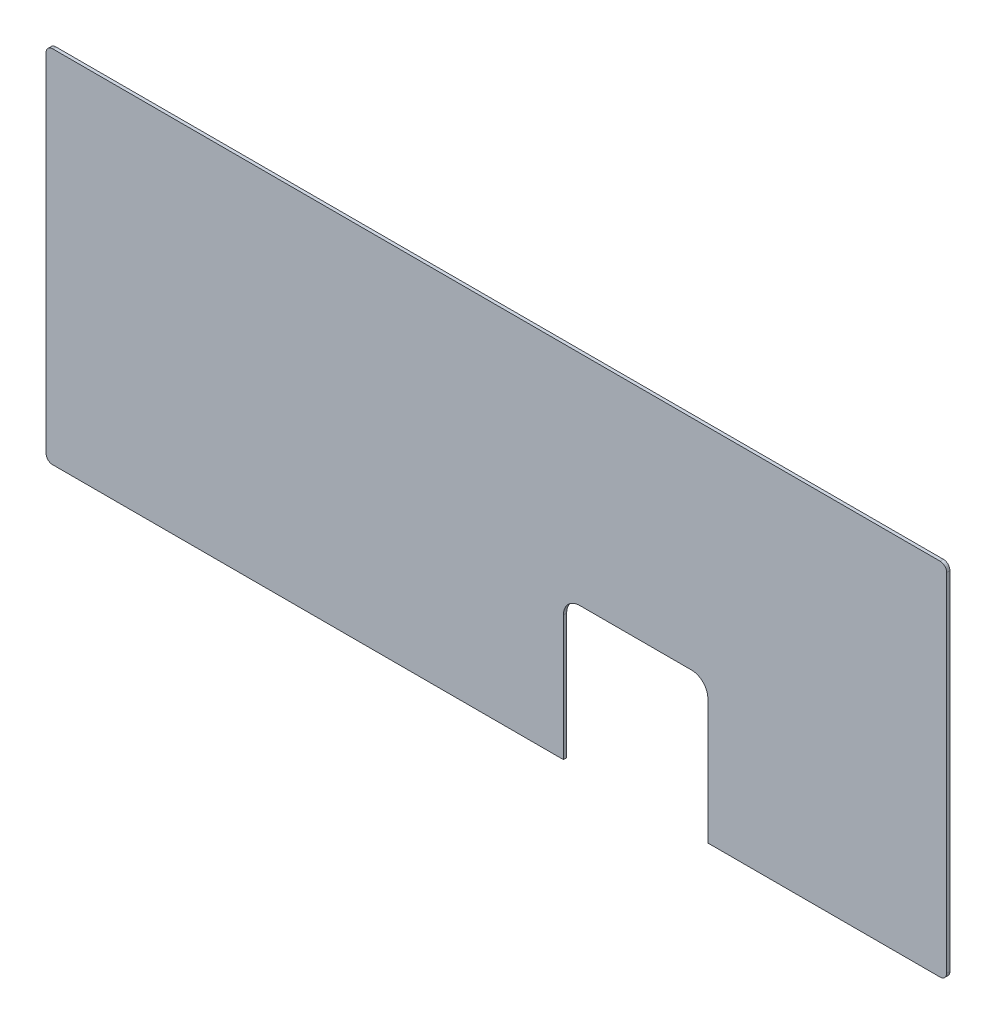
SolidWorks part; units mm, degrees
ref_plane "Спереди" through (0, 0, 0) normal (0, 0, 1) x (1, 0, 0)
ref_plane "Сверху" through (0, 0, 0) normal (0, 1, 0) x (1, 0, 0)
ref_plane "Справа" through (0, 0, 0) normal (1, 0, 0) x (0, 0, -1)
sketch "Эскиз1" plane through (0, 0, 0) normal (0, 0, 1) x (1, 0, 0)
  line L0 (89.221, -66.774) -> (89.221, -28.5207)
  line L1 (-66.75, -66.774) -> (89.221, -66.774)
  line L2 (-68.75, -64.774) -> (-68.75, 41.226)
  line L3 (-66.75, 43.226) -> (204.25, 43.226)
  line L4 (206.25, -64.774) -> (206.25, 41.226)
  line L5 (-68.75, -66.774) -> (206.25, 43.226) construction
  line L6 (-68.75, 43.226) -> (206.25, -66.774) construction
  line L7 (94.221, -23.5207) -> (128.3293, -23.5207)
  line L8 (133.3293, -28.5207) -> (133.3293, -66.774)
  line L9 (133.3293, -66.774) -> (204.25, -66.774)
  arc A0 (-66.75, -66.774) -> (-68.75, -64.774) centre (-66.75, -64.774) cw
  arc A1 (206.25, -64.774) -> (204.25, -66.774) centre (204.25, -64.774) cw
  arc A2 (206.25, 41.226) -> (204.25, 43.226) centre (204.25, 41.226) ccw
  arc A3 (-66.75, 43.226) -> (-68.75, 41.226) centre (-66.75, 41.226) ccw
  arc A4 (133.3293, -28.5207) -> (128.3293, -23.5207) centre (128.3293, -28.5207) ccw
  arc A5 (94.221, -23.5207) -> (89.221, -28.5207) centre (94.221, -28.5207) ccw
  point P0 (0, 0)
  dimension "D3" = 2
  dimension "D4" = 5
  dimension "D1" = 275
  dimension "D2" = 110
base flange "Базовая кромка1" sketch "Эскиз1" thickness 1 reverse thickness direction no parameters "D1"=0.7366
sketch "Сгиб-Линии1" [suppressed]
sketch "Граничная рамка1" [suppressed]
sheet metal parameters "Листовой металл1" thickness 1 parameters "D1"=0.7366
flat pattern "Развертка1" [suppressed]
sketch "Сгиб-Линии2" plane through (0, 0, 0) normal (0, 1, 0) x (1, 0, 0)
sketch3d "Граничная рамка2" [suppressed]
  line L0 (-68.75, -66.774, 0) -> (206.25, -66.774, 0) construction
  line L1 (-68.75, 43.226, 0) -> (206.25, 43.226, 0) construction
  line L2 (-68.75, -66.774, 0) -> (-68.75, 43.226, 0) construction
  line L3 (206.25, -66.774, 0) -> (206.25, 43.226, 0) construction
